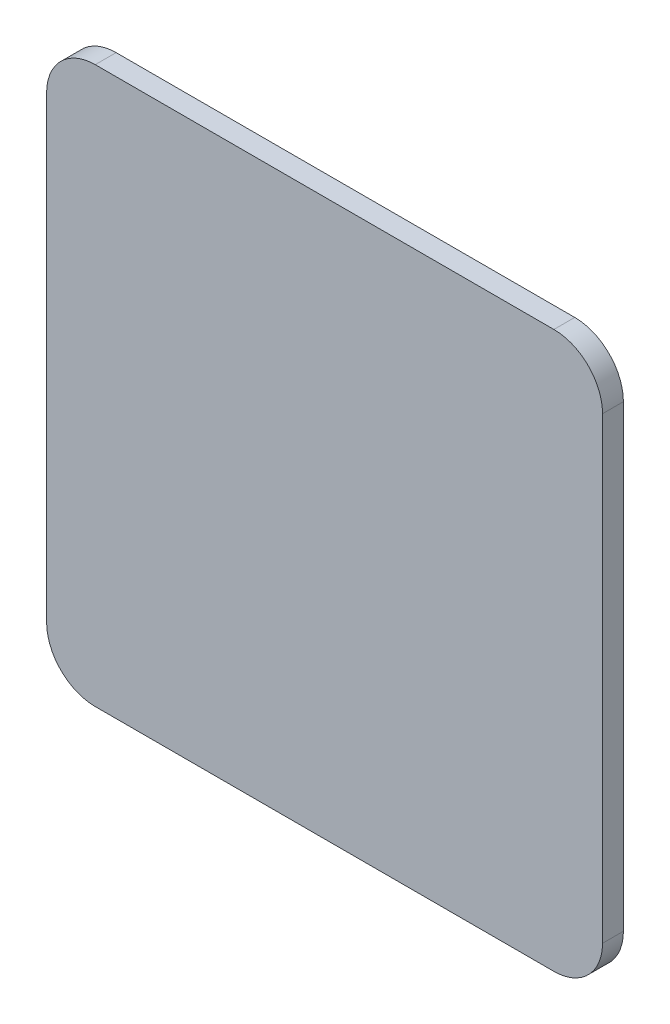
SolidWorks part; units mm, degrees
material "ABS PC"
ref_plane "Front Plane" through (0, 0, 0) normal (0, 0, 1) x (1, 0, 0)
ref_plane "Top Plane" through (0, 0, 0) normal (0, 1, 0) x (1, 0, 0)
ref_plane "Right Plane" through (0, 0, 0) normal (1, 0, 0) x (0, 0, -1)
sketch "Sketch1" plane through (0, 0, 0) normal (0, 0, 1) x (1, 0, 0)
  line L1 (-40, -40) -> (40, -40)
  line L2 (-40, -40) -> (-40, 40)
  line L3 (-40, 40) -> (40, 40)
  line L4 (40, -40) -> (40, 40)
  line L5 (-40, -40) -> (40, 40) construction
  line L6 (-40, 40) -> (40, -40) construction
  point P0 (0, 0)
  dimension "D1" = 80
  dimension "D2" = 80
extrude "Boss-Extrude1" add sketch "Sketch1" along normal blind 3
fillet "Fillet1" radius 7 4 edges at (-40, 40, 1.5) (-40, -40, 1.5) (40, -40, 1.5) (40, 40, 1.5)
